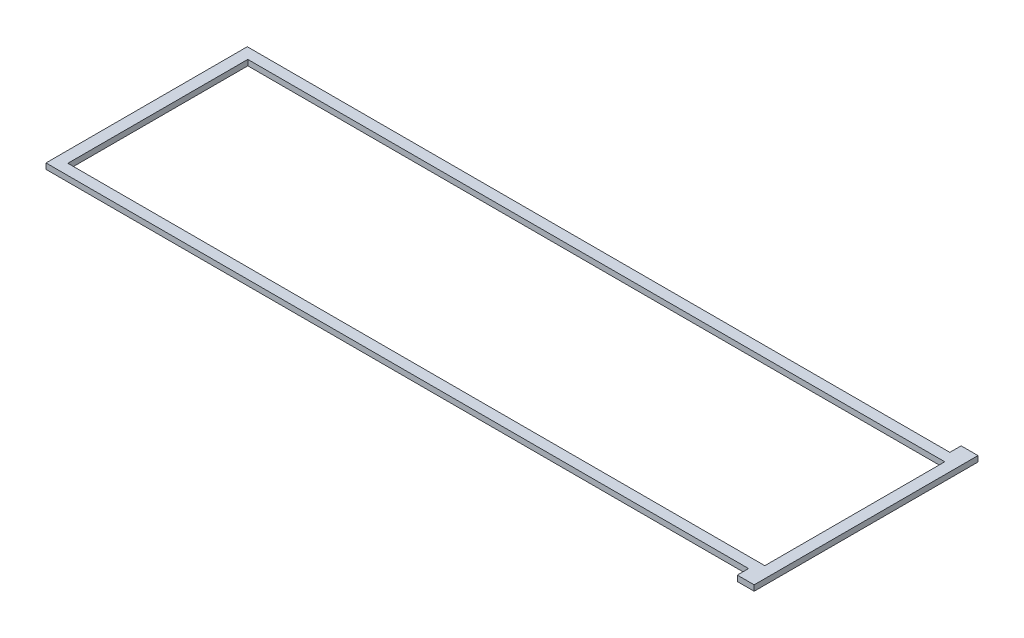
SolidWorks part; units mm, degrees
ref_plane "Front" through (0, 0, 0) normal (0, 0, 1) x (1, 0, 0)
ref_plane "Top" through (0, 0, 0) normal (0, 1, 0) x (1, 0, 0)
ref_plane "Right" through (0, 0, 0) normal (1, 0, 0) x (0, 0, -1)
sketch "Sketch1" plane through (0, 0, 0) normal (0, 1, 0) x (1, 0, 0)
  line L1 (-203.2, -63.2238) -> (203.2, -63.2238)
  line L2 (-203.2, -63.2238) -> (-203.2, 63.2238)
  line L3 (-203.2, 63.2238) -> (203.2, 63.2238)
  line L4 (203.2, -63.2238) -> (203.2, 63.2238)
  line L5 (-203.2, -63.2238) -> (203.2, 63.2238) construction
  line L6 (-203.2, 63.2238) -> (203.2, -63.2238) construction
  line L7 (-203.2, 63.2238) -> (193.675, 63.2238)
  line L8 (-203.2, 63.2238) -> (-203.2, 56.8484)
  line L9 (-203.2, 56.8484) -> (193.675, 56.8484)
  line L10 (193.675, 63.2238) -> (193.675, 56.8484)
  line L11 (-203.2, -63.2238) -> (193.675, -63.2238)
  line L12 (-203.2, -63.2238) -> (-203.2, -56.8484)
  line L13 (-203.2, -56.8484) -> (193.675, -56.8484)
  line L14 (193.675, -63.2238) -> (193.675, -56.8484)
  line L15 (-196.85, -50.8508) -> (196.85, -50.8508)
  line L16 (-196.85, -50.8508) -> (-196.85, 50.8)
  line L17 (-196.85, 50.8) -> (196.85, 50.8)
  line L18 (196.85, -50.8508) -> (196.85, 50.8)
  point P0 (0, 0)
  point P12 (0, 0)
  dimension "D1" = 126.4475
  dimension "D2" = 406.4
  dimension "D3" = 9.525
  dimension "D4" = 6.3754
  dimension "D5" = 101.6508
  dimension "D6" = 6.35
  dimension "D7" = 50.8
  dimension "D8" = 6.35
extrude "Boss-Extrude1" add sketch "Sketch1" along normal blind 3.175 contours L14 L1 L4 L3 L10 L9 L2 L13 L18 L15 L16 L17 region at (197.9312, 0, 60.0361)
equation "\"D1@Sketch1\"    = 4.98025 - 0.002"
